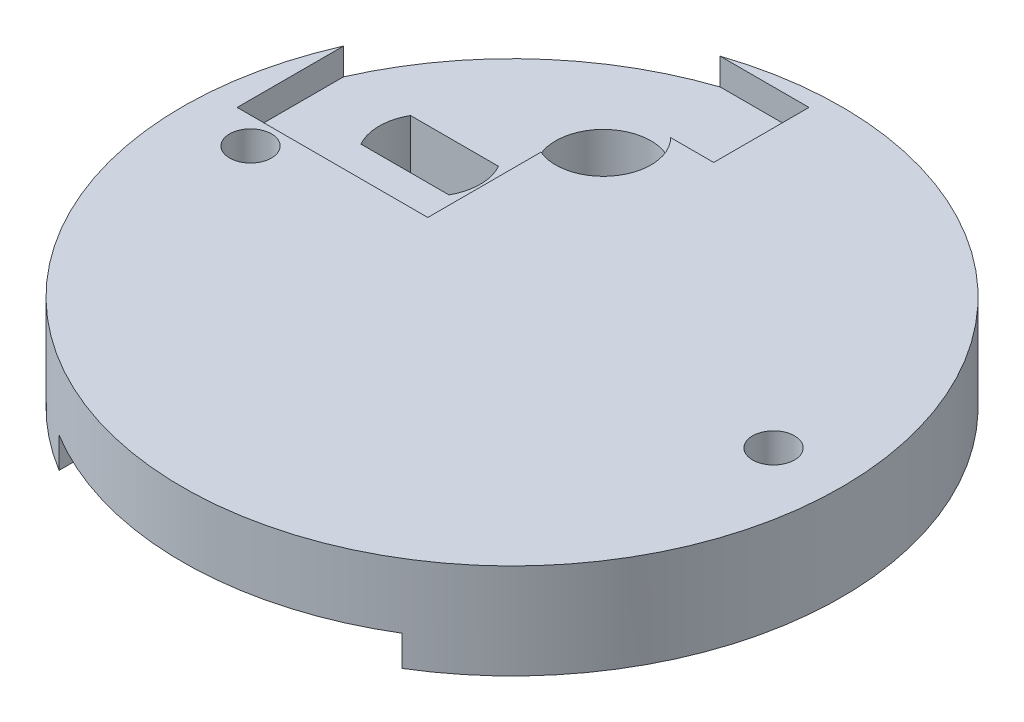
SolidWorks part; units mm, degrees
ref_plane "前视基准面" through (0, 0, 0) normal (0, 0, 1) x (1, 0, 0)
ref_plane "上视基准面" through (0, 0, 0) normal (0, 1, 0) x (1, 0, 0)
ref_plane "右视基准面" through (0, 0, 0) normal (1, 0, 0) x (0, 0, -1)
sketch "草图1" plane through (0, 0, 0) normal (0, 1, 0) x (1, 0, 0)
  line L0 (0, 0) -> (-27.1848, 0) construction
  line L1 (0, 0) -> (0, -9.0346) construction
  line L2 (-12.3092, 6.98) -> (-7.6908, 6.98)
  line L3 (-12.3092, 4.38) -> (-7.6908, 4.38)
  line L4 (12.3092, 6.98) -> (7.6908, 6.98)
  line L5 (12.3092, 4.38) -> (7.6908, 4.38)
  circle A0 centre (0, 0) radius 17.29
  circle A1 centre (-13.72, 0) radius 1.1
  circle A2 centre (13.72, 0) radius 1.1
  circle A3 centre (-4.85, 9.64) radius 2.5
  arc A5 (-12.3092, 6.98) -> (-12.3092, 4.38) centre (-10, 5.68) ccw
  arc A8 (-7.6908, 4.38) -> (-7.6908, 6.98) centre (-10, 5.68) ccw
  arc A9 (12.3092, 6.98) -> (12.3092, 4.38) centre (10, 5.68) cw
  arc A10 (7.6908, 4.38) -> (7.6908, 6.98) centre (10, 5.68) cw
  dimension "D1" = 34.58
  dimension "D2" = 13.72
  dimension "D4" = 2.2
  dimension "D5" = 2.2
  dimension "D6" = 4.85
  dimension "D8" = 5
  dimension "D9" = 5.3
  dimension "D10" = 2.6
  dimension "D3" = 13.72
  dimension "D7" = 9.64
  dimension "D11" = 10
  dimension "D12" = 5.68
  dimension "D13" = 1.3
extrude "凸台-拉伸1" add sketch "草图1" along normal blind 4
sketch "草图2" plane through (0, 0, 0) normal (0, -1, 0) x (1, 0, 0)
  line L0 (0, 0) -> (20.6825, 0) construction
  line L1 (-9.22, 3.3) -> (-5.22, 3.3)
  line L2 (-9.22, 3.3) -> (-9.22, -1.5)
  line L3 (-9.22, -1.5) -> (-5.22, -1.5)
  line L4 (-5.22, 3.3) -> (-5.22, -1.5)
  line L5 (0, 0.7878) -> (0, -6.0913) construction
  line L6 (6, 0.6) -> (10, 0.6)
  line L7 (6, 0.6) -> (6, -2.8)
  line L8 (6, -2.8) -> (10, -2.8)
  line L9 (10, 0.6) -> (10, -2.8)
  line L10 (-17.196, 5.8) -> (-12.796, 5.8)
  line L11 (-17.196, 5.8) -> (-17.196, 1.8)
  line L12 (-17.196, 1.8) -> (-12.796, 1.8)
  line L13 (-12.796, 5.8) -> (-12.796, 1.8)
  line L19 (-9, 5.29) -> (9, 5.29)
  line L20 (-9, 5.29) -> (-9, 17.29)
  line L21 (-9, 17.29) -> (9, 17.29)
  line L22 (9, 5.29) -> (9, 17.29)
  line L23 (-9, 5.29) -> (9, 17.29) construction
  line L24 (-9, 17.29) -> (9, 5.29) construction
  circle A0 centre (-13.72, 0) radius 1.1 construction
  circle A1 centre (0, 0) radius 17.29 construction
  point P22 (0, 11.29)
  dimension "D3" = 4.5
  dimension "D5" = 3.4
  dimension "D1" = 4
  dimension "D2" = 4.8
  dimension "D4" = 1.5
  dimension "D6" = 4
  dimension "D7" = 6
  dimension "D8" = 2.8
  dimension "D9" = 4
  dimension "D10" = 1.8
  dimension "D11" = 4.4
  dimension "D12" = 12
  dimension "D13" = 18
extrude "切除-拉伸1" cut sketch "草图2" against normal blind 1.6
sketch "草图3" plane through (0, 4, 0) normal (0, 1, 0) x (1, 0, 0)
  circle A0 centre (0, 0) radius 17.29 construction
  circle A1 centre (0, 0) radius 17.29
  circle A2 centre (-4.85, 9.64) radius 2.5 construction
  circle A3 centre (-4.85, 9.64) radius 2.5
  circle A4 centre (-13.72, 0) radius 1.1 construction
  circle A5 centre (-13.72, 0) radius 1.1
  circle A6 centre (13.72, 0) radius 1.1 construction
  circle A7 centre (13.72, 0) radius 1.1
extrude "凸台-拉伸2" add sketch "草图3" along normal blind 1
sketch "草图4" plane through (0, 5, 0) normal (0, 1, 0) x (1, 0, 0)
  line L0 (0, 0) -> (6.0206, 0) construction
  line L1 (-15.82, 16.4) -> (-5.82, 16.4)
  line L2 (-15.82, 16.4) -> (-15.82, 1.4)
  line L3 (-15.82, 1.4) -> (-5.82, 1.4)
  line L4 (-5.82, 11.4) -> (-5.82, 1.4)
  line L5 (0, 0) -> (0, -7.8731) construction
  line L7 (-5.82, 16.4) -> (-0.82, 16.4)
  line L9 (-5.82, 11.4) -> (-0.82, 11.4)
  line L10 (-0.82, 16.4) -> (-0.82, 11.4)
  circle A1 centre (-13.72, 0) radius 1.1 construction
  circle A2 centre (-13.72, 0) radius 1.1 construction
  circle A3 centre (-13.72, 0) radius 2.1 construction
  dimension "D3" = 1
  dimension "D1" = 10
  dimension "D2" = 15
  dimension "D4" = 1.4
  dimension "D5" = 5
  dimension "D6" = 5
  dimension "D7" = 10
extrude "切除-拉伸2" cut sketch "草图4" against normal blind 1.4
